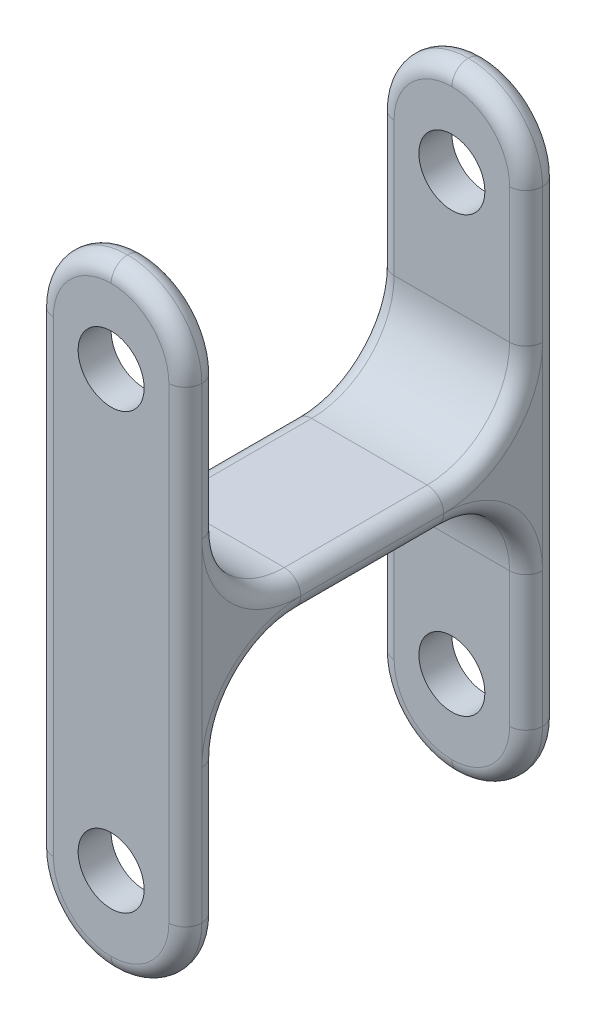
SolidWorks part; units mm, degrees
ref_plane "Front Plane" through (0, 0, 0) normal (0, 0, 1) x (1, 0, 0)
ref_plane "Top Plane" through (0, 0, 0) normal (0, 1, 0) x (1, 0, 0)
ref_plane "Right Plane" through (0, 0, 0) normal (1, 0, 0) x (0, 0, -1)
sketch "Sketch1" plane through (0, 0, 0) normal (1, 0, 0) x (0, 0, -1)
  line L0 (0, 0) -> (0, -37.34)
  line L1 (0, -37.34) -> (2, -37.34)
  line L2 (2, -37.34) -> (2, -19.67)
  line L3 (2, -19.67) -> (20.66, -19.67)
  line L4 (20.66, -19.67) -> (20.66, -37.34)
  line L5 (20.66, -37.34) -> (22.66, -37.34)
  line L6 (22.66, -37.34) -> (22.66, 0)
  line L7 (22.66, 0) -> (20.66, 0)
  line L8 (20.66, 0) -> (20.66, -17.67)
  line L9 (20.66, -17.67) -> (2, -17.67)
  line L10 (2, -17.67) -> (2, 0)
  line L11 (2, 0) -> (0, 0)
  point P11 (0, 0)
  dimension "D1" = 37.34
  dimension "D2" = 2
  dimension "D3" = 2
  dimension "D4" = 22.66
extrude "Boss-Extrude1" add sketch "Sketch1" along normal blind 9
sketch "Sketch2" plane through (0, 0, 0) normal (0, 0, 1) x (1, 0, 0)
  line L0 (4.5, 0) -> (4.5, -37.34) construction
  line L1 (9, 0) -> (0, 0) construction
  line L2 (9, -37.34) -> (0, -37.34) construction
  circle A0 centre (4.5, -5.5) radius 2
  circle A1 centre (4.5, -31.84) radius 2
  dimension "D1" = 4
  dimension "D2" = 4
  dimension "D3" = 5.5
  dimension "D4" = 5.5
extrude "Cut-Extrude1" cut sketch "Sketch2" against normal through all
fillet "Fillet1" radius 5 4 edges at (4.5, -19.67, -2) (4.5, -19.67, -20.66) (4.5, -17.67, -2) (4.5, -17.67, -20.66)
fillet "Fillet3" radius 4.5 8 edges at (9, 0, -1) (0, 0, -1) (9, 0, -21.66) (0, 0, -21.66) (0, -37.34, -1) (9, -37.34, -1) (9, -37.34, -21.66) (0, -37.34, -21.66)
fillet "Fillet4" radius 1 40 edges at (7.682, -36.022, -22.66) (1.318, -36.022, -22.66) (0, -18.67, -22.66) (1.318, -1.318, -22.66) (7.682, -1.318, -22.66) (7.682, -1.318, 0) (1.318, -1.318, 0) (0, -18.67, 0) (1.318, -36.022, 0) (7.682, -36.022, 0) (9, -19.67, -11.33) (9, -21.1345, -3.4645) (9, -28.755, -2) (7.682, -36.022, -2) (1.318, -36.022, -2) (0, -28.755, -2) (0, -21.1345, -3.4645) (0, -19.67, -11.33) (0, -21.1345, -19.1955) (0, -28.755, -20.66) (1.318, -36.022, -20.66) (7.682, -36.022, -20.66) (9, -28.755, -20.66) (9, -8.585, -20.66) (7.682, -1.318, -20.66) (1.318, -1.318, -20.66) (0, -8.585, -20.66) (0, -16.2055, -19.1955) (0, -17.67, -11.33) (0, -16.2055, -3.4645) (0, -8.585, -2) (1.318, -1.318, -2) (7.682, -1.318, -2) (9, -8.585, -2) (9, -16.2055, -3.4645) (9, -17.67, -11.33) (9, -18.67, -22.66) (9, -18.67, 0) (9, -21.1345, -19.1955) (9, -16.2055, -19.1955)
